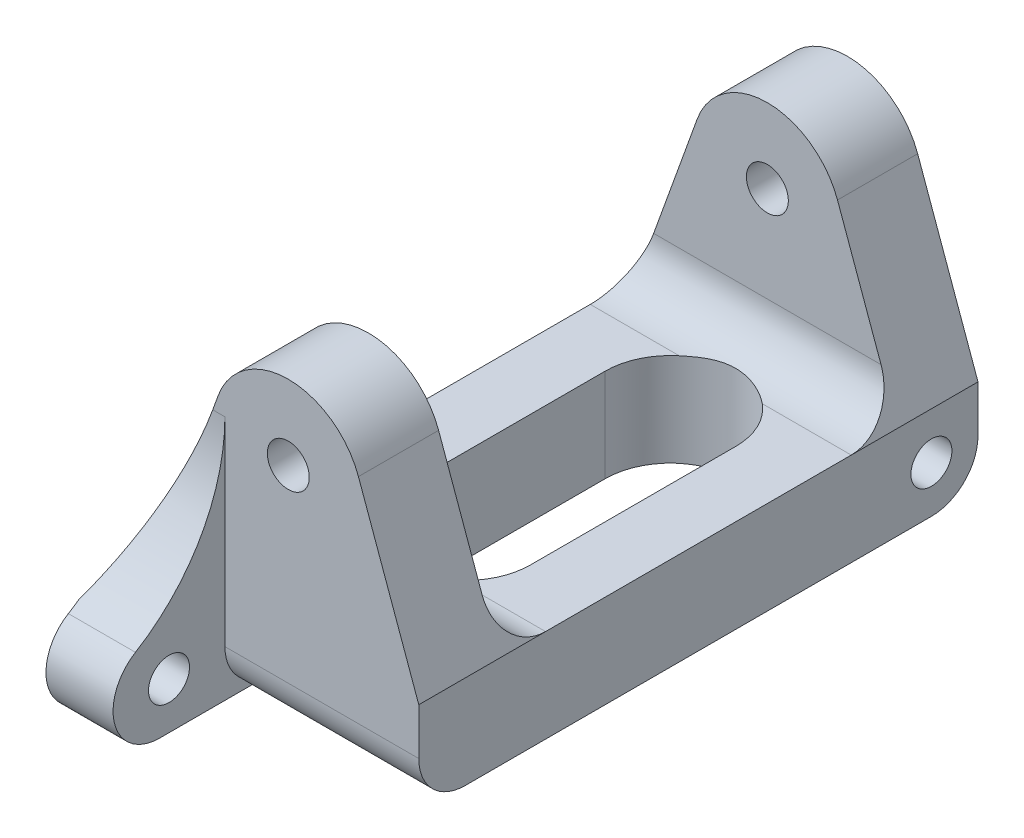
SolidWorks part; units mm, degrees
ref_plane "Front Plane" through (0, 0, 0) normal (0, 0, 1) x (1, 0, 0)
ref_plane "Top Plane" through (0, 0, 0) normal (0, 1, 0) x (1, 0, 0)
ref_plane "Right Plane" through (0, 0, 0) normal (1, 0, 0) x (0, 0, -1)
sketch "Sketch1" plane through (0, 0, 0) normal (0, 1, 0) x (1, 0, 0)
  line L0 (-7, 0) -> (7, 0)
  line L1 (-7, -15) -> (7, -15)
  line L2 (-7, -15) -> (-7, 15)
  line L3 (-7, 15) -> (7, 15)
  line L4 (7, -15) -> (7, 15)
  line L5 (-7, -15) -> (7, 15) construction
  line L6 (-7, 15) -> (7, -15) construction
  point P0 (0, 0)
  dimension "D1" = 30
  dimension "D2" = 14
extrude "Boss-Extrude1" add sketch "Sketch1" against normal blind 5 contours L0 L4 L3 L2 region at (0, 0, -7.5)
sketch "Sketch3" plane through (-7, 0, 0) normal (-1, 0, 0) x (0, 0, 1)
  line L0 (-15, -2.5) -> (-12.5, -2.5) construction
  line L1 (-15, -5) -> (-15, 0) construction
  circle A0 centre (-12.5, -2.5) radius 1.1
  dimension "D1" = 2.2
  dimension "D2" = 2.5
extrude "Cut-Extrude1" cut sketch "Sketch3" against normal up to surface (14 mm away) up to face at (7, -2.5, -7.5)
ref_plane "Plane1" through (0, 0, -10.7) normal (0, 0, 1) x (1, 0, 0)
sketch "Sketch4" plane through (0, 0, -15) normal (0, 0, -1) x (-1, 0, 0)
  line L0 (0, 0) -> (0, 7.625) construction
  line L1 (7, 0) -> (-7, 0) construction
  line L2 (-7, 0) -> (-3.7631, 8.9812)
  line L3 (7, 0) -> (3.7631, 8.9812)
  line L4 (7, 0) -> (-7, 0)
  line L5 (7, -5) -> (-7, -5) construction
  arc A0 (3.7631, 8.9812) -> (-3.7631, 8.9812) centre (0, 7.625) ccw
  dimension "D2" = 8
  dimension "D1" = 12.625
extrude "Boss-Extrude2" add sketch "Sketch4" against normal up to surface (4.3 mm away) up to plane "Plane1"
sketch "Sketch5" plane through (0, 0, -15) normal (0, 0, -1) x (-1, 0, 0)
  circle A0 centre (0, 7.625) radius 1.125
  arc A1 (3.7631, 8.9812) -> (-3.7631, 8.9812) centre (0, 7.625) ccw construction
  dimension "D1" = 2.25
extrude "Cut-Extrude2" cut sketch "Sketch5" against normal up to surface (4.3 mm away) up to face at (0, 5.1516, -10.7)
fillet "Fillet1" radius 2.5 2 edges at (0, -5, -15) (0, 0, -10.7)
sketch "Sketch6" plane through (0, 0, 0) normal (0, 1, 0) x (1, 0, 0)
  line L0 (0, -5.5) -> (0, 5.5) construction
  line L1 (-3.5, -5.5) -> (-3.5, 5.5)
  line L2 (3.5, -5.5) -> (3.5, 5.5)
  arc A0 (-3.5, -5.5) -> (3.5, -5.5) centre (0, -5.5) ccw
  arc A1 (3.5, 5.5) -> (-3.5, 5.5) centre (0, 5.5) ccw
  point P2 (0, 0)
  dimension "D2" = 3.5
  dimension "D1" = 11
extrude "Cut-Extrude3" cut sketch "Sketch6" against normal up to surface (5 mm away) and the other way up to surface up to face at (0, -5, -6.25) other way up to face at (0, 0.9911, -9.7089)
mirror "Mirror1" about plane through (0, 0, 0) normal (0, 0, 1) of bodies 105
sketch "Sketch7" plane through (7, 0, 0) normal (1, 0, 0) x (0, 0, -1)
  line L0 (-12.5, -2.5) -> (-18.5, -2.5) construction
  line L1 (-12.5, -5) -> (-18.5, -5)
  line L2 (-12.5, 0) -> (-18.5, 0)
  line L3 (-12.5, -5) -> (12.5, -5) construction
  line L4 (-15, -2.5) -> (-15, 0) construction
  arc A0 (-12.5, -5) -> (-12.5, 0) centre (-12.5, -2.5) ccw
  arc A1 (-18.5, 0) -> (-18.5, -5) centre (-18.5, -2.5) ccw
  circle A2 centre (-18, -2.5) radius 1.1
  point P3 (-15.5, -2.5)
  dimension "D1" = 2.2
  dimension "D2" = 3.5
  dimension "D3" = 3
extrude "Boss-Extrude4" add sketch "Sketch7" against normal blind 3.6 from offset 10.4 offset against normal yes
sketch "Sketch8" plane through (7, 0, 0) normal (1, 0, 0) x (0, 0, -1)
  circle A1 centre (-12.5, -2.5) radius 1.1 construction
  circle A2 centre (-12.5, -2.5) radius 1.1
extrude "Boss-Extrude5" add sketch "Sketch8" against normal up to surface (10.4 mm away) up to face at (-3.4, -2.5, 11.4)
fillet "Fillet2" radius 10 1 edges at (-5.2, 0, 15)
